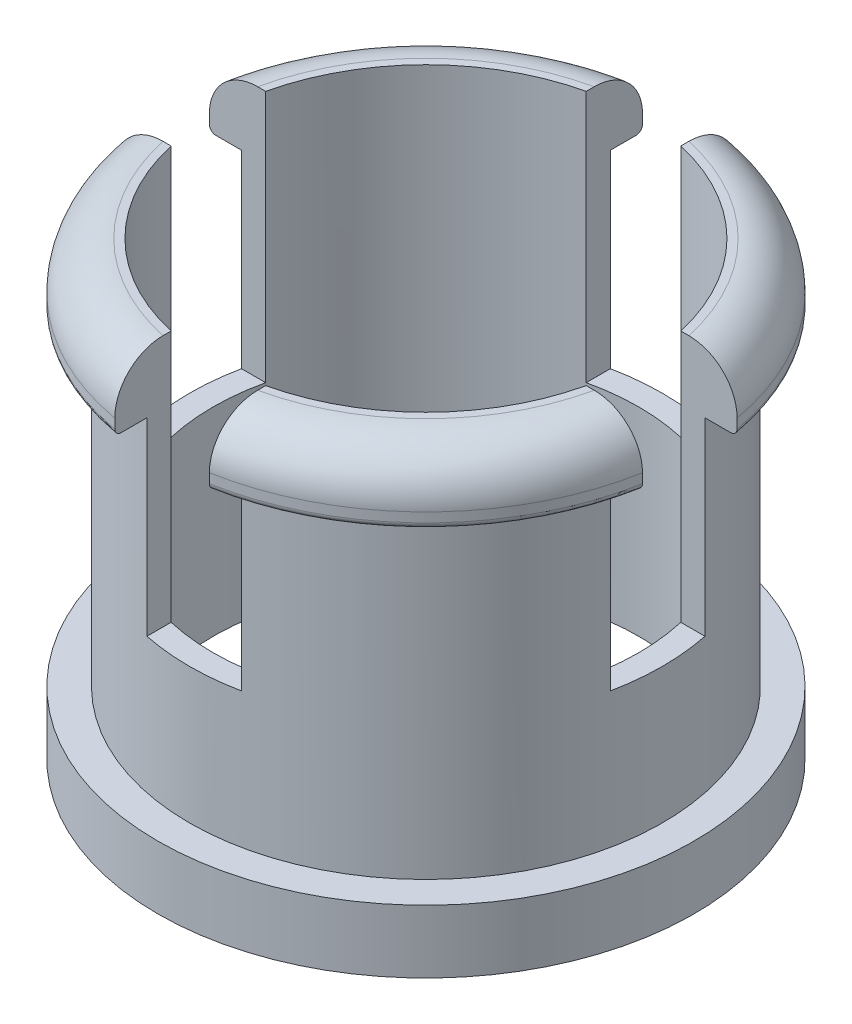
SolidWorks part; units mm, degrees
ref_plane "Front Plane" through (0, 0, 0) normal (0, 0, 1) x (1, 0, 0)
ref_plane "Top Plane" through (0, 0, 0) normal (0, 1, 0) x (1, 0, 0)
ref_plane "Right Plane" through (0, 0, 0) normal (1, 0, 0) x (0, 0, -1)
sketch "Sketch1" plane through (0, 0, 0) normal (0, 1, 0) x (1, 0, 0)
  line L1 (-9, 1.5) -> (9, 1.5)
  line L2 (-9, 1.5) -> (-9, -1.5)
  line L3 (-9, -1.5) -> (9, -1.5)
  line L4 (9, 1.5) -> (9, -1.5)
  line L5 (-9, 1.5) -> (9, -1.5) construction
  line L6 (-9, -1.5) -> (9, 1.5) construction
  circle A0 centre (0, 0) radius 7.5
  circle A1 centre (0, 0) radius 6.75
  circle A2 centre (0, 0) radius 8.5
  dimension "D1" = 15
  dimension "D2" = 13.5
  dimension "D3" = 17
  dimension "D4" = 18
  dimension "D5" = 3
extrude "Boss-Extrude1" add sketch "Sketch1" along normal blind 10.3 contours L3 A1 | L3 A1 L1 | L1 A1 | A0 region at (0, 0, -3.6909) region at (0, 0, 0) region at (0, 0, 3.6909)
extrude "Boss-Extrude2" add sketch "Sketch1<3>" against normal blind 2 contours L1 A1 | L3 A1 L1 | L3 A1 | A2 region at (0, 0, -3.6909) region at (0, 0, 0) region at (0, 0, 3.6909)
sketch "Sketch1<3>" plane through (0, 0, 0) normal (0, 1, 0) x (1, 0, 0) same geometry as "Sketch1"
extrude "Boss-Extrude3" add sketch "Sketch1<4>" along normal blind 2 from surface contours L3 A1 | L3 A1 L1 | L1 A1 | A2 region at (0, 0, -3.6909) region at (0, 0, 0) region at (0, 0, 3.6909) starting at face at (0, 10.3, 7.5)
sketch "Sketch1<4>" plane through (0, 0, 0) normal (0, 1, 0) x (1, 0, 0) same geometry as "Sketch1"
fillet "Fillet1" radius 1.5 1 edges at (0, 12.3, 8.5)
fillet "Fillet2" radius 0.2 1 edges at (0, 10.3, 8.5)
extrude "Cut-Extrude1" cut sketch "Sketch1<6>" against normal blind 8 from surface contours L2 L3 L4 L1 starting at face at (0, 12.3, 7)
sketch "Sketch1<6>" plane through (0, 0, 0) normal (0, 1, 0) x (1, 0, 0) same geometry as "Sketch1"
sketch "Sketch3" plane through (0, 0, 0) normal (0, 1, 0) x (1, 0, 0)
  line L1 (-1.5, 11.3257) -> (1.5, 11.3257)
  line L2 (-1.5, 11.3257) -> (-1.5, -11.3257)
  line L3 (-1.5, -11.3257) -> (1.5, -11.3257)
  line L4 (1.5, 11.3257) -> (1.5, -11.3257)
  line L5 (-1.5, 11.3257) -> (1.5, -11.3257) construction
  line L6 (-1.5, -11.3257) -> (1.5, 11.3257) construction
  point P0 (0, 0)
  dimension "D1" = 3
extrude "Cut-Extrude3" cut sketch "Sketch3" against normal up to surface (-4.3 mm away) from surface up to face at (7.0449, 4.3, 0) starting at face at (0, 12.3, -4.1875)
